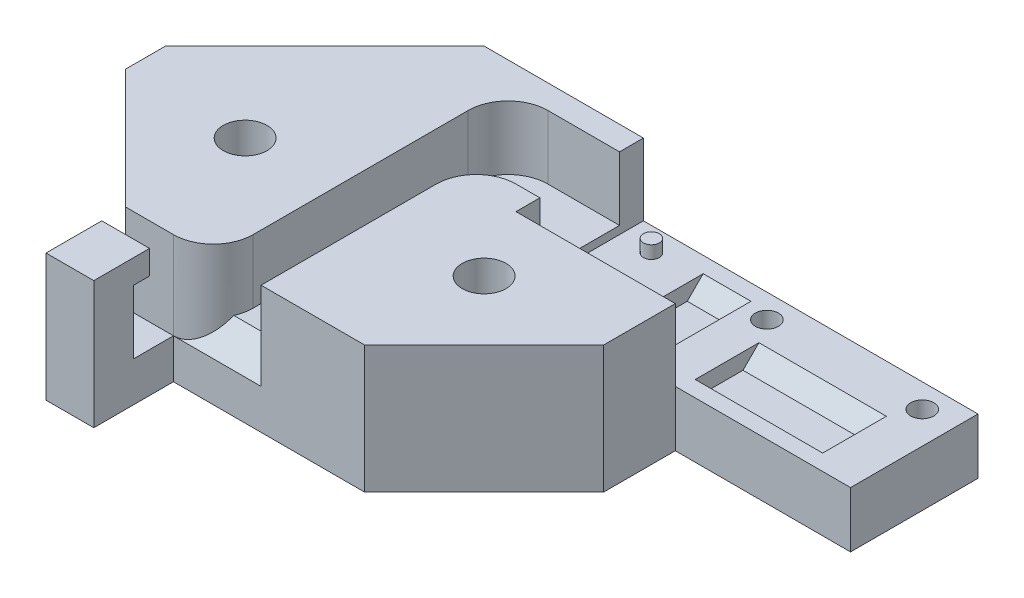
SolidWorks part; units mm, degrees
ref_plane "Front Plane" through (0, 0, 0) normal (0, 0, 1) x (1, 0, 0)
ref_plane "Top Plane" through (0, 0, 0) normal (0, 1, 0) x (1, 0, 0)
ref_plane "Right Plane" through (0, 0, 0) normal (1, 0, 0) x (0, 0, -1)
sketch "Sketch1" plane through (0, 0, 0) normal (0, 1, 0) x (1, 0, 0)
  line L1 (-21, 8) -> (21, 8)
  line L2 (-21, 8) -> (-21, -8)
  line L3 (-21, -8) -> (21, -8)
  line L4 (21, 8) -> (21, -8)
  line L5 (-21, 8) -> (21, -8) construction
  line L6 (-21, -8) -> (21, 8) construction
  point P0 (0, 0)
  dimension "D1" = 42
  dimension "D2" = 16
extrude "Boss-Extrude1" add sketch "Sketch1" along normal blind 7
sketch "Sketch2" plane through (0, 7, 0) normal (0, 1, 0) x (1, 0, 0)
  line L0 (21, 8) -> (-21, 8) construction
  line L1 (-21, -8) -> (21, -8) construction
  line L2 (-21, 8) -> (-21, -8) construction
  circle A0 centre (-17, 5) radius 1
  circle A1 centre (-17, -5) radius 1
  dimension "D1" = 2
  dimension "D2" = 2
  dimension "D3" = 3
  dimension "D4" = 3
  dimension "D5" = 4
  dimension "D6" = 4
extrude "Boss-Extrude2" add sketch "Sketch2" along normal blind 1.6
sketch "Sketch3" plane through (0, 0, 0) normal (0, 1, 0) x (1, 0, 0)
  line L0 (21, -8) -> (21, 8) construction
  line L1 (21, 8) -> (-21, 8) construction
  line L2 (-21, 8) -> (-21, -8) construction
  circle A0 centre (-2.5, 5) radius 1.45
  circle A1 centre (17, 5) radius 1.45
  dimension "D5" = 2.9
  dimension "D6" = 2.9
  dimension "D1" = 4
  dimension "D2" = 3
  dimension "D3" = 3
  dimension "D4" = 18.5
extrude "Cut-Extrude1" cut sketch "Sketch3" along normal up to next
sketch "Sketch4" plane through (0, 0, 0) normal (0, 1, 0) x (1, 0, 0)
  line L0 (-1, -8) -> (-21, -8)
  line L1 (-61, 8) -> (-21, 8)
  line L2 (-61, 8) -> (-61, -32)
  line L3 (-61, -32) -> (-1, -32)
  line L4 (-21, -8) -> (-21, 8)
  line L6 (-1, -8) -> (-1, -32)
  dimension "D1" = 40
  dimension "D2" = 40
  dimension "D3" = 60
  dimension "D4" = 16
  dimension "D5" = 20
extrude "Boss-Extrude3" add sketch "Sketch4" along normal blind 16
sketch "Sketch5" plane through (0, 0, 0) normal (0, 1, 0) x (1, 0, 0)
  line L1 (-61, 8) -> (-61, -32) construction
  line L2 (-61, -32) -> (-1, -32) construction
  circle A0 centre (-46, -17) radius 2.75
  circle A1 centre (-16, -17) radius 2.75
  dimension "D1" = 5.5
  dimension "D2" = 5.5
  dimension "D3" = 15
  dimension "D4" = 15
  dimension "D5" = 15
  dimension "D6" = 45
extrude "Cut-Extrude2" cut sketch "Sketch5" along normal up to next
ref_plane "Plane1" through (-40, 0, 0) normal (1, 0, 0) x (0, 0, -1)
sketch "Sketch6" plane through (-40, 0, 0) normal (1, 0, 0) x (0, 0, -1)
  line L0 (-32, 0) -> (-42, 0)
  line L1 (27.5, 0) -> (-27.5, 0) construction
  line L2 (-32, 16) -> (-32, 0) construction
  line L3 (-42, 0) -> (-42, 16)
  line L4 (-42, 16) -> (-35, 16)
  line L5 (-35, 16) -> (-35, 13)
  line L6 (-35, 13) -> (-37, 13)
  line L7 (-37, 13) -> (-37, 5)
  line L8 (-37, 5) -> (-32, 5)
  line L9 (-32, 5) -> (-32, 0)
  dimension "D1" = 5
  dimension "D2" = 16
  dimension "D3" = 3
  dimension "D4" = 5
  dimension "D5" = 2
  dimension "D6" = 7
extrude "Boss-Extrude4" add sketch "Sketch6" against normal blind 6
sketch "Sketch7" plane through (0, 16, 0) normal (0, 1, 0) x (1, 0, 0)
  line L0 (-21, 5) -> (-21, -5)
  line L3 (-21, -5) -> (-29, -5)
  line L4 (-29, -5) -> (-29, -32)
  line L5 (-61, -32) -> (-1, -32) construction
  line L6 (-29, -32) -> (-35, -32)
  line L7 (-35, -32) -> (-35, 5)
  line L8 (-35, 5) -> (-21, 5)
  line L9 (-21, 8) -> (-61, 8) construction
  line L10 (-61, 8) -> (-61, -32) construction
  dimension "D1" = 14
  dimension "D2" = 3
  dimension "D3" = 10
  dimension "D5" = 6
  dimension "D7" = 26
extrude "Cut-Extrude3" cut sketch "Sketch7" against normal blind 8
fillet "Fillet1" radius 5 3 edges at (-35, 12, 32) (-35, 12, -5) (-29, 12, 5)
chamfer "Chamfer2" distance 3 angle 45 1 edges at (-34.5, 8, 32)
chamfer "Chamfer3" distance 15 angle 45 2 edges at (-1, 8, 32) (-61, 8, 32)
chamfer "Chamfer5" distance 20 angle 45 1 edges at (-61, 8, -8)
sketch "Sketch8" plane through (0, 7, 0) normal (0, 1, 0) x (1, 0, 0)
  line L0 (21, 8) -> (-21, 8) construction
  line L1 (-0.5, 0) -> (15.5, 0)
  line L2 (-0.5, 0) -> (-0.5, -4)
  line L3 (-0.5, -4) -> (15.5, -4)
  line L4 (15.5, 0) -> (15.5, -4)
  line L5 (-11.5, 6) -> (-5.5, 6)
  line L6 (-11.5, 6) -> (-11.5, -4)
  line L7 (-11.5, -4) -> (-5.5, -4)
  line L8 (-5.5, 6) -> (-5.5, -4)
  line L9 (21, -8) -> (21, 8) construction
  line L10 (-1, -8) -> (21, -8) construction
  line L11 (-21, 8) -> (-21, -8) construction
  dimension "D1" = 6
  dimension "D2" = 4
  dimension "D3" = 16
  dimension "D4" = 10
  dimension "D5" = 2
  dimension "D6" = 5.5
  dimension "D7" = 4
  dimension "D8" = 9.5
extrude "Cut-Extrude4" cut sketch "Sketch8" against normal blind 2
chamfer "Chamfer6" distance 2 angle 45 4 edges at (7.5, 7, 4) (7.5, 7, 0) (-8.5, 7, 4) (-8.5, 5, -6)
